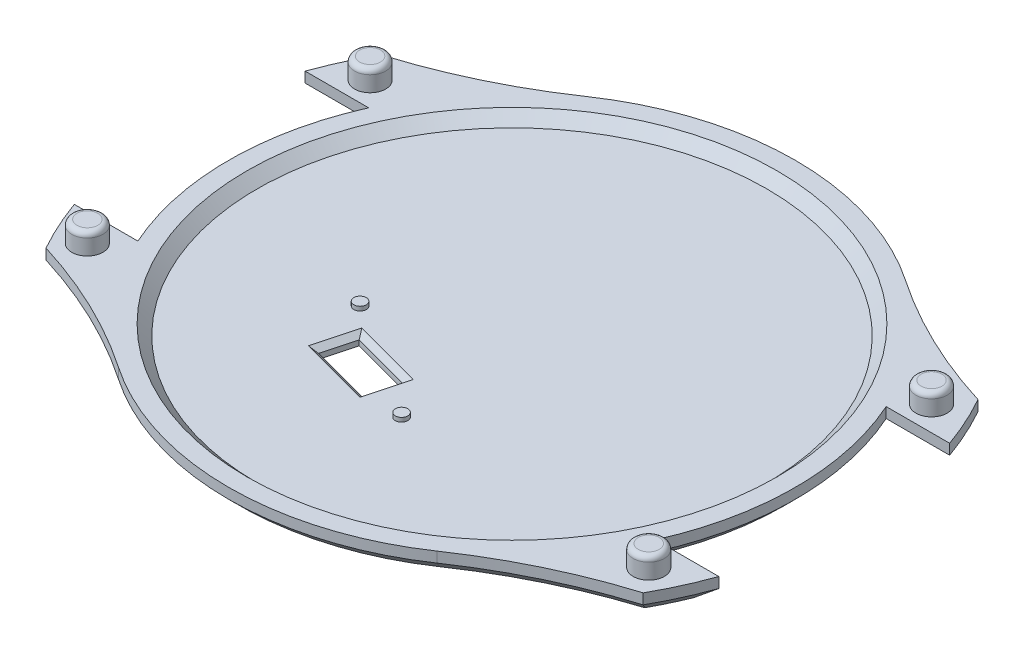
SolidWorks part; units mm, degrees
ref_plane "Front Plane" through (0, 0, 0) normal (0, 0, 1) x (1, 0, 0)
ref_plane "Top Plane" through (0, 0, 0) normal (0, 1, 0) x (1, 0, 0)
ref_plane "Right Plane" through (0, 0, 0) normal (1, 0, 0) x (0, 0, -1)
sketch "Sketch1" plane through (0, 0, 0) normal (0, 1, 0) x (1, 0, 0)
  line L0 (-31, 11.1) -> (-24.8868, 11.1)
  line L1 (-31, -11.1) -> (-24.8868, -11.1)
  line L2 (31, -11.1) -> (24.8868, -11.1)
  line L3 (31, 11.1) -> (24.8868, 11.1)
  circle A0 centre (0, 0) radius 27.25
  circle A1 centre (0, 0) radius 25.5
  circle A2 centre (-27.1282, 13.4815) radius 1.2
  arc A3 (-31, 11.1) -> (-28.7228, 16.1) centre (0, 0) cw
  arc A4 (-28.7228, -16.1) -> (-15.3178, -22.5372) centre (-43.424, -63.8899) cw
  arc A5 (-28.7228, 16.1) -> (-15.3178, 22.5372) centre (-43.424, 63.8899) ccw
  circle A6 centre (-27.1282, -13.7185) radius 1.2
  arc A7 (-31, -11.1) -> (-28.7228, -16.1) centre (0, 0) ccw
  arc A8 (31, -11.1) -> (28.7228, -16.1) centre (0, 0) cw
  circle A9 centre (26.8718, -13.7185) radius 1.2
  arc A10 (28.7228, -16.1) -> (15.3178, -22.5372) centre (43.424, -63.8899) ccw
  arc A11 (28.7228, 16.1) -> (15.3178, 22.5372) centre (43.424, 63.8899) cw
  arc A12 (31, 11.1) -> (28.7228, 16.1) centre (0, 0) ccw
  circle A13 centre (26.8718, 13.4815) radius 1.2
extrude "Boss-Extrude1" add sketch "Sketch1" along normal blind 2 contours A5 A3 L0 A0 A2 | L1 A7 A4 A0 A6 | A0 A1 | A10 A8 L2 A0 A9 | L3 A12 A11 A0 A13 region at (-25.3171, 0, -15.0049) region at (-20.3088, 0, -16.9913) region at (-25.3171, 0, 14.9788) region at (25.3453, 0, -15.0049) region at (25.3453, 0, 14.9788)
sketch "Sketch2" plane through (0, 0, 0) normal (0, -1, 0) x (1, 0, 0)
  circle A0 centre (0, 0) radius 25.5
extrude "Boss-Extrude3" add sketch "Sketch2" against normal blind 1
sketch "Sketch3" plane through (0, 0, 0) normal (0, -1, 0) x (1, 0, 0)
  circle A0 centre (-27.1282, 13.7185) radius 1.5
  circle A1 centre (26.8718, 13.7185) radius 1.5
  circle A2 centre (26.8718, -13.4815) radius 1.5
  circle A3 centre (-27.1282, -13.4815) radius 1.5
extrude "Boss-Extrude4" add sketch "Sketch3" against normal blind 4
chamfer "Chamfer1" distance 1 angle 45 16 edges at (-29.9659, 0, -13.6476) (-27.9434, 0, -11.1) (-27.25, 0, 0) (-27.9434, 0, 11.1) (-29.9659, 0, 13.6476) (-21.7797, 0, 18.8175) (0, 0, 27.25) (21.7797, 0, 18.8175) (29.9659, 0, 13.6476) (27.9434, 0, 11.1) (27.25, 0, 0) (27.9434, 0, -11.1) (29.9659, 0, -13.6476) (21.7797, 0, -18.8175) (0, 0, -27.25) (-21.7797, 0, -18.8175)
chamfer "Chamfer2" distance 1 angle 45 1 edges at (0, 1, -25.5)
sketch "Sketch4" plane through (0, 1, 0) normal (0, 1, 0) x (1, 0, 0)
  line L0 (-7.5185, -7.1811) -> (-1.7229, -8.734)
  line L1 (-7.5185, -7.1811) -> (-8.3467, -10.2721)
  line L2 (-1.7229, -8.734) -> (-2.5512, -11.825)
  line L3 (-8.3467, -10.2721) -> (-2.5512, -11.825)
  dimension "D3" = 3.2
  dimension "D4" = 6
  dimension "D5" = 6
extrude "Cut-Extrude1" cut sketch "Sketch4" against normal blind 2
sketch "Sketch5" plane through (0, 1, 0) normal (0, 1, 0) x (1, 0, 0)
  circle A0 centre (1.4609, -12.082) radius 0.6
  circle A1 centre (-9.7935, -4.8218) radius 0.6
  dimension "D1" = 1.2
  dimension "D2" = 1.2
extrude "Boss-Extrude5" add sketch "Sketch5" along normal blind 0.4
chamfer "Chamfer3" distance 0.5 angle 45 4 edges at (-2.1371, 1, 10.2795) (-4.6207, 1, 7.9576) (-7.9326, 1, 8.7266) (-5.4489, 1, 11.0486)
fillet "Fillet1" radius 0.5 4 edges at (-27.1282, 4, 12.2185) (-27.1282, 4, -14.9815) (26.8718, 4, -14.9815) (26.8718, 4, 12.2185)
